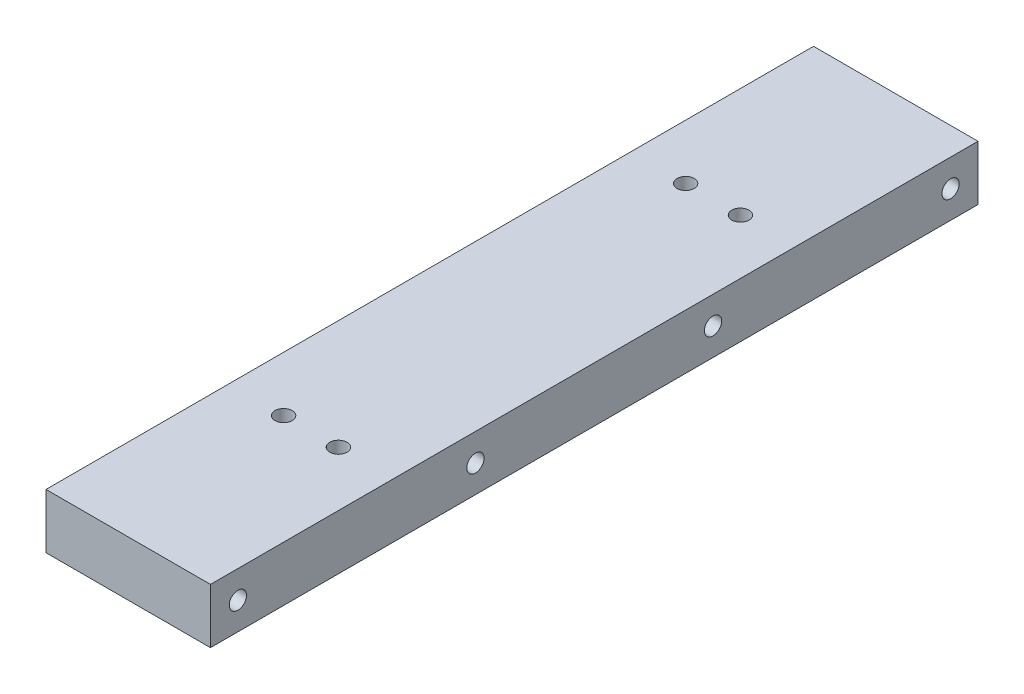
SolidWorks part; units mm, degrees
ref_plane "Front Plane" through (0, 0, 0) normal (0, 0, 1) x (1, 0, 0)
ref_plane "Top Plane" through (0, 0, 0) normal (0, 1, 0) x (1, 0, 0)
ref_plane "Right Plane" through (0, 0, 0) normal (1, 0, 0) x (0, 0, -1)
sketch "Sketch2" plane through (0, 0, 0) normal (0, 1, 0) x (1, 0, 0)
  line L0 (0, 0) -> (28.575, 0)
  line L1 (28.575, 0) -> (28.575, 133.35)
  line L2 (28.575, 133.35) -> (0, 133.35)
  line L3 (0, 133.35) -> (0, 0)
  dimension "D1" = 133.35
  dimension "D2" = 28.575
extrude "Boss-Extrude1" add sketch "Sketch2" along normal blind 9.525
sketch "Sketch3" plane through (28.575, 0, 0) normal (1, 0, 0) x (0, 0, -1)
  line L0 (0, 9.525) -> (0, 0) construction
  line L1 (0, 9.525) -> (133.35, 9.525) construction
  point P0 (4.7625, 4.7625)
  dimension "D1" = 4.7625
  dimension "D2" = 4.7625
sketch "Sketch4" plane through (28.575, 0, 0) normal (1, 0, 0) x (0, 0, -1)
  point P0 (4.7625, 4.7625)
hole_wizard "Ø3.0mm Dowel Hole1" positions "Sketch4" profile "Sketch5" hole size "Ø3.0" standard "ANSI Metric" end condition through all
sketch "Sketch5" plane through (28.575, 4.7625, -4.7625) normal (0, 1, 0) x (0, 0, -1)
  line L0 (0, 0) -> (0, 28.575)
  line L1 (0, 28.575) -> (1.5, 28.575)
  line L2 (1.5, 28.575) -> (1.5, 0)
  line L5 (1.5, 0) -> (0, 0)
  line L11 (0, -6.35) -> (0, 107.95) construction
  dimension "Thru Hole Dia." = 3
  dimension "Thru Hole Depth" = 28.575
pattern_linear "LPattern1" count 4 spacing 41.275 along (0, 0, -1) of "Ø3.0mm Dowel Hole1"
sketch "Sketch8" plane through (0, 0, 0) normal (0, -1, 0) x (1, 0, 0)
  line L0 (0, 0) -> (14.2875, 0)
  line L1 (0, 0) -> (28.575, 0) construction
  line L2 (28.575, -133.35) -> (0, -133.35) construction
  line L3 (0, -133.35) -> (0, 0) construction
  line L4 (28.575, 0) -> (28.575, -133.35) construction
  circle A0 centre (9.525, -31.75) radius 1.5
  circle A1 centre (9.525, -101.6) radius 1.5
  circle A2 centre (19.05, -101.6) radius 1.5
  circle A3 centre (19.05, -31.75) radius 1.5
  point P5 (9.525, -31.75)
  point P6 (9.525, -101.6)
  point P15 (19.05, -31.75)
  point P16 (19.05, -101.6)
  dimension "D5" = 3
  dimension "D6" = 3
  dimension "D11" = 3
  dimension "D12" = 3
  dimension "D1" = 31.75
  dimension "D2" = 31.75
  dimension "D3" = 9.525
  dimension "D4" = 9.525
  dimension "D7" = 9.525
  dimension "D8" = 9.525
  dimension "D9" = 31.75
  dimension "D10" = 31.75
extrude "Cut-Extrude2" cut sketch "Sketch8" against normal through all contours A0 | A1 | A2 | A3 region at (9.525, 0, -31.75) region at (9.525, 0, -101.6)
